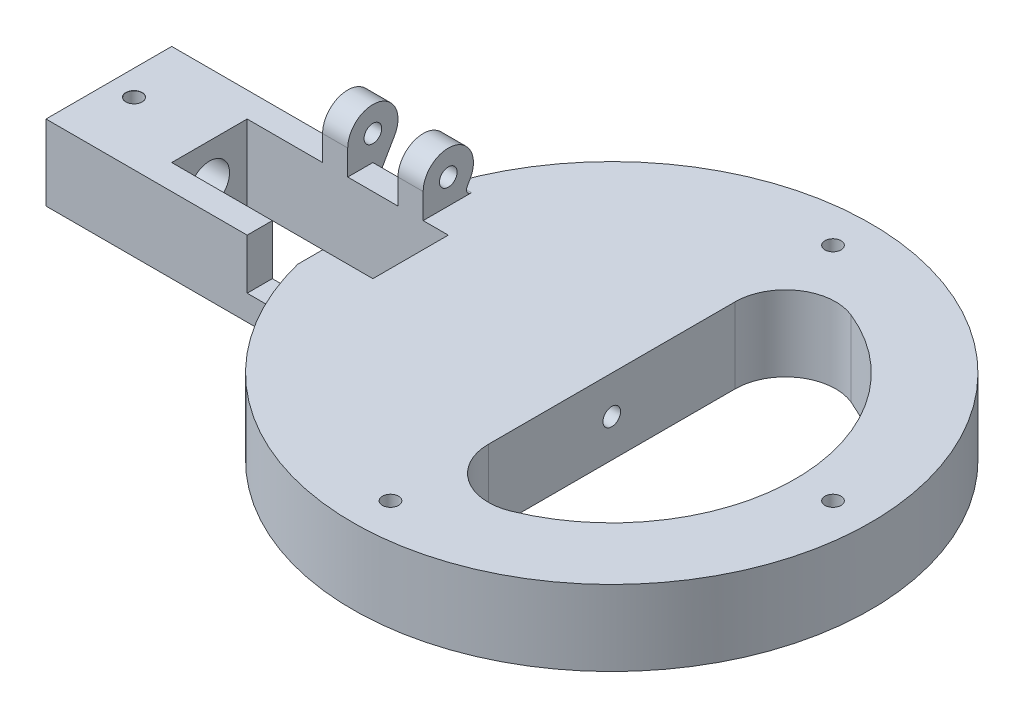
SolidWorks part; units mm, degrees
ref_plane "Front Plane" through (0, 0, 0) normal (0, 0, 1) x (1, 0, 0)
ref_plane "Top Plane" through (0, 0, 0) normal (0, 1, 0) x (1, 0, 0)
ref_plane "Right Plane" through (0, 0, 0) normal (1, 0, 0) x (0, 0, -1)
sketch "Sketch2" plane through (0, 0, 0) normal (0, 1, 0) x (1, 0, 0)
  line L1 (-20, -7.5) -> (20, -7.5)
  line L2 (-20, -7.5) -> (-20, 7.5)
  line L3 (-20, 7.5) -> (20, 7.5)
  line L4 (20, -7.5) -> (20, 7.5)
  line L5 (-20, -7.5) -> (20, 7.5) construction
  line L6 (-20, 7.5) -> (20, -7.5) construction
  line L7 (-40, -12.5) -> (60, -12.5)
  line L8 (-40, -12.5) -> (-40, 12.5)
  line L9 (-40, 12.5) -> (60, 12.5)
  line L10 (60, -12.5) -> (60, 12.5)
  point P0 (0, 0)
  point P10 (-40, 0)
  dimension "D1" = 15
  dimension "D2" = 25
  dimension "D3" = 20
  dimension "D4" = 40
  dimension "D5" = 40
extrude "Boss-Extrude1" add sketch "Sketch2" along normal blind 15
sketch "Sketch3" plane through (60, 0, 0) normal (1, 0, 0) x (0, 0, -1)
  line L0 (0, 0) -> (0, 7.5) construction
  line L1 (-12.5, 0) -> (12.5, 0) construction
  circle A0 centre (0, 7.5) radius 1.75
  dimension "D1" = 3.5
  dimension "D2" = 7.5
extrude "Cut-Extrude1" cut sketch "Sketch3" against normal up to next
sketch "Sketch4" plane through (-40, 0, 0) normal (-1, 0, 0) x (0, 0, 1)
  circle A0 centre (0, 7.5) radius 4
  dimension "D2" = 8
  dimension "D1" = 7.5
extrude "Cut-Extrude2" cut sketch "Sketch4" against normal up to next
sketch "Sketch7" plane through (0, 15, 0) normal (0, 1, 0) x (1, 0, 0)
  line L0 (-40, 12.5) -> (-40, -12.5) construction
  point P0 (-35, 0)
  dimension "D1" = 5
hole_wizard "Ø3.2 (3.2) Diameter Hole1" positions "Sketch7" profile "Sketch6" hole size "Ø3.2" standard "ANSI Metric" end condition through all
sketch "Sketch6" plane through (-35, 15, 0) normal (1, 0, 0) x (0, 0, 1)
  line L0 (0, 0) -> (0, 15)
  line L1 (0, 15) -> (1.6, 15)
  line L2 (1.6, 15) -> (1.6, 0.025)
  line L3 (1.6, 0.025) -> (1.625, 0)
  line L5 (1.625, 0) -> (0, 0)
  line L6 (-1.6, 0.025) -> (-1.625, 0) construction
  line L11 (0, -6.35) -> (0, 107.95) construction
  dimension "Thru Hole Dia." = 3.2
  dimension "Thru Hole Depth" = 15
  dimension "Near C'Sink Dia." = 3.25
  dimension "Near C'Sink Angle" = 90
sketch "Sketch9" plane through (-20, 0, 0) normal (1, 0, 0) x (0, 0, -1)
  line L0 (7.5, 15) -> (12.5, 15)
  line L1 (12.5, 15) -> (12.5, 10)
  line L4 (7.5, 20) -> (7.5, 15)
  line L7 (12.5, 10) -> (16.8301, 17.5)
  line L8 (12.5, 15) -> (12.5, 0) construction
  circle A0 centre (12.5, 20) radius 1.75
  arc A1 (16.8301, 17.5) -> (7.5, 20) centre (12.5, 20) ccw
  point P2 (16.6794, 16.0514)
  point P4 (12.5, 20)
  point P5 (13.4079, 20)
  point P7 (0, 0)
  dimension "D1" = 3.5
  dimension "D2" = 5
  dimension "D3" = 5
extrude "Boss-Extrude3" add sketch "Sketch9" along normal blind 40
sketch "Sketch12" plane through (0, 0, -7.5) normal (0, 0, 1) x (1, 0, 0)
  line L0 (20, 20) -> (20, 15) construction
  line L1 (-20, 15) -> (-5, 15)
  line L2 (-20, 15) -> (-20, 30)
  line L3 (-20, 30) -> (-5, 30)
  line L4 (-5, 15) -> (-5, 30)
  line L5 (0, 15) -> (10, 15)
  line L6 (0, 15) -> (0, 30)
  line L7 (0, 30) -> (10, 30)
  line L8 (10, 15) -> (10, 30)
  line L9 (15, 15) -> (20, 15)
  line L10 (15, 15) -> (15, 30)
  line L11 (15, 30) -> (20, 30)
  line L12 (20, 15) -> (20, 30)
  dimension "D1" = 5
  dimension "D2" = 5
  dimension "D3" = 15
  dimension "D4" = 15
  dimension "D5" = 10
extrude "Cut-Extrude3" cut sketch "Sketch12" against normal through all
sketch "Sketch11" plane through (0, 0, 0) normal (0, -1, 0) x (1, 0, 0)
  line L5 (60, 12.5) -> (60, 36.5)
  line L7 (60, 12.5) -> (10.04, 12.5)
  line L9 (60, 12.5) -> (60, -12.5) construction
  line L15 (60, -12.5) -> (60, -36.5)
  line L17 (10.04, -12.5) -> (60, -12.5)
  circle A0 centre (60, 0) radius 44 construction
  circle A1 centre (60, 44) radius 1.6
  circle A2 centre (60, -44) radius 1.6
  circle A3 centre (104, 0) radius 1.6
  arc A4 (60, -36.5) -> (60, 36.5) centre (60, 0) ccw
  arc A5 (10.04, -12.5) -> (10.04, 12.5) centre (60, 0) ccw
  dimension "D1" = 88
  dimension "D2" = 3.2
  dimension "D3" = 15
  dimension "D4" = 7.5
extrude "Boss-Extrude4" add sketch "Sketch11" against normal blind 15
fillet "Fillet1" radius 10 2 edges at (60, 7.5, 36.5) (60, 7.5, -36.5)
sketch "Sketch13" plane through (0, 15, 0) normal (0, 1, 0) x (1, 0, 0)
  line L0 (-5, 17.5) -> (-5, 7.5) construction
  line L1 (-20, 15.3868) -> (-5, 15.3868)
  line L2 (-20, 15.3868) -> (-20, 12.5)
  line L3 (-20, 12.5) -> (-5, 12.5)
  line L4 (-5, 15.3868) -> (-5, 12.5)
  line L5 (10, 15.3868) -> (10, 7.5) construction
  line L6 (0, 15.3868) -> (10, 15.3868)
  line L7 (0, 15.3868) -> (0, 12.5)
  line L8 (0, 12.5) -> (10, 12.5)
  line L9 (10, 15.3868) -> (10, 12.5)
  line L10 (-20, 12.5) -> (-40, 12.5) construction
extrude "Cut-Extrude4" cut sketch "Sketch13" against normal through all
fillet "Fillet3" radius 1 2 edges at (-2.5, 10, -12.5) (12.9261, 15, -15.3868)
sketch "Sketch14" plane through (0, 15, 0) normal (0, 1, 0) x (1, 0, 0)
  line L0 (-20, -7.5) -> (20, -7.5) construction
  line L1 (0, -7.5) -> (10.04, -7.5)
  line L2 (0, -7.5) -> (0, -12.5)
  line L3 (0, -12.5) -> (10.04, -12.5)
  line L4 (10.04, -7.5) -> (10.04, -12.5)
extrude "Cut-Extrude5" cut sketch "Sketch14" against normal blind 10
